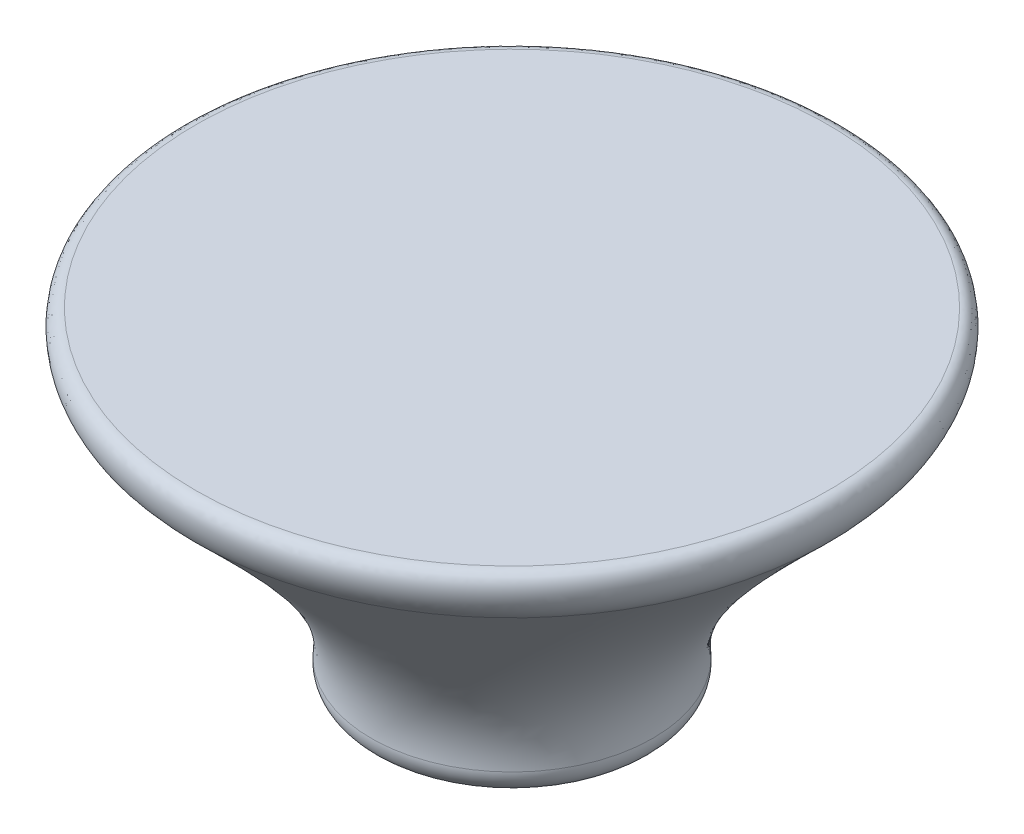
SolidWorks part; units mm, degrees
ref_plane "Front Plane" through (0, 0, 0) normal (0, 0, 1) x (1, 0, 0)
ref_plane "Top Plane" through (0, 0, 0) normal (0, 1, 0) x (1, 0, 0)
ref_plane "Right Plane" through (0, 0, 0) normal (1, 0, 0) x (0, 0, -1)
sketch "Sketch1" plane through (0, 0, 0) normal (0, 1, 0) x (1, 0, 0)
  circle A0 centre (0, 0) radius 1.7
  circle A1 centre (0, 0) radius 6.7
  dimension "D1" = 3.4
  dimension "D2" = 5
ref_plane "Plane1" through (0, 15, 0) normal (0, 1, 0) x (1, 0, 0)
sketch "Sketch2" plane through (0, 15, 0) normal (0, 1, 0) x (1, 0, 0)
  circle A0 centre (0, 0) radius 1.7 construction
  circle A1 centre (0, 0) radius 1.7
  circle A2 centre (0, 0) radius 16.7
  dimension "D1" = 15
loft "Loft1" add section "Sketch2" section "Sketch1" connector at (-3.9087, 15, -16.2361) connector at (6.3007, 0, -2.2785)
fillet "Fillet1" radius 2 1 edges at (0, 15, 16.7) second distance 0.05 first distance on face at (0, 15, 16.7)
extrude "Cut-Extrude1" cut sketch "Sketch1<3>" along normal blind 10 contours A0 region at (0, 0, 0)
sketch "Sketch1<3>" plane through (0, 0, 0) normal (0, 1, 0) x (1, 0, 0) same geometry as "Sketch1"
fillet "Fillet2" radius 1 1 edges at (0, 0, 6.7)
